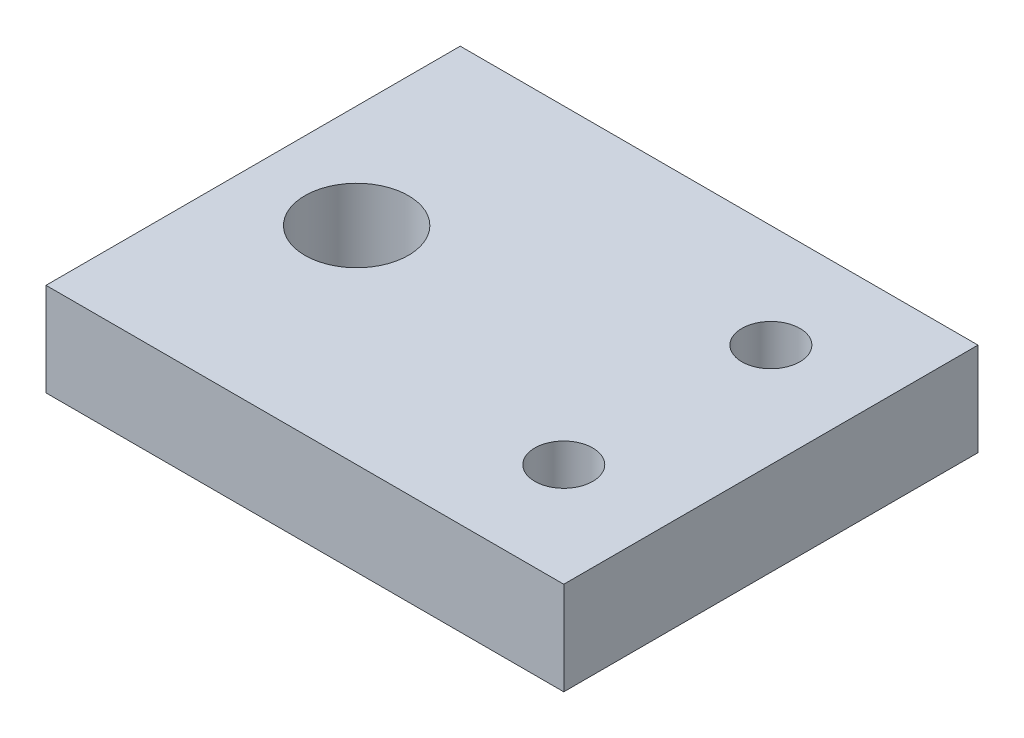
SolidWorks part; units mm, degrees
ref_plane "Front Plane" through (0, 0, 0) normal (0, 0, 1) x (1, 0, 0)
ref_plane "Top Plane" through (0, 0, 0) normal (0, 1, 0) x (1, 0, 0)
ref_plane "Right Plane" through (0, 0, 0) normal (1, 0, 0) x (0, 0, -1)
sketch "Sketch1" plane through (0, 0, 0) normal (0, 1, 0) x (1, 0, 0)
  line L0 (20, 15) -> (20, 5) construction
  line L1 (0, 0) -> (25, 0)
  line L2 (0, 0) -> (0, 20)
  line L3 (0, 20) -> (25, 20)
  line L4 (25, 0) -> (25, 20)
  circle A0 centre (5, 10) radius 2.5
  circle A1 centre (20, 15) radius 1.4
  circle A2 centre (20, 5) radius 1.4
  point P11 (20, 10)
  dimension "D3" = 5
  dimension "D5" = 2.8
  dimension "D1" = 20
  dimension "D2" = 10
  dimension "D4" = 5
  dimension "D6" = 10
  dimension "D7" = 15
  dimension "D8" = 25
extrude "Boss-Extrude1" add sketch "Sketch1" along normal blind 4.5 contours L3 L4 L1 L2
extrude "Cut-Extrude1" cut sketch "Sketch1<4>" along normal blind 4.5 contours A1 | A0 | A2
sketch "Sketch1<4>" plane through (0, 0, 0) normal (0, 1, 0) x (1, 0, 0) same geometry as "Sketch1"
